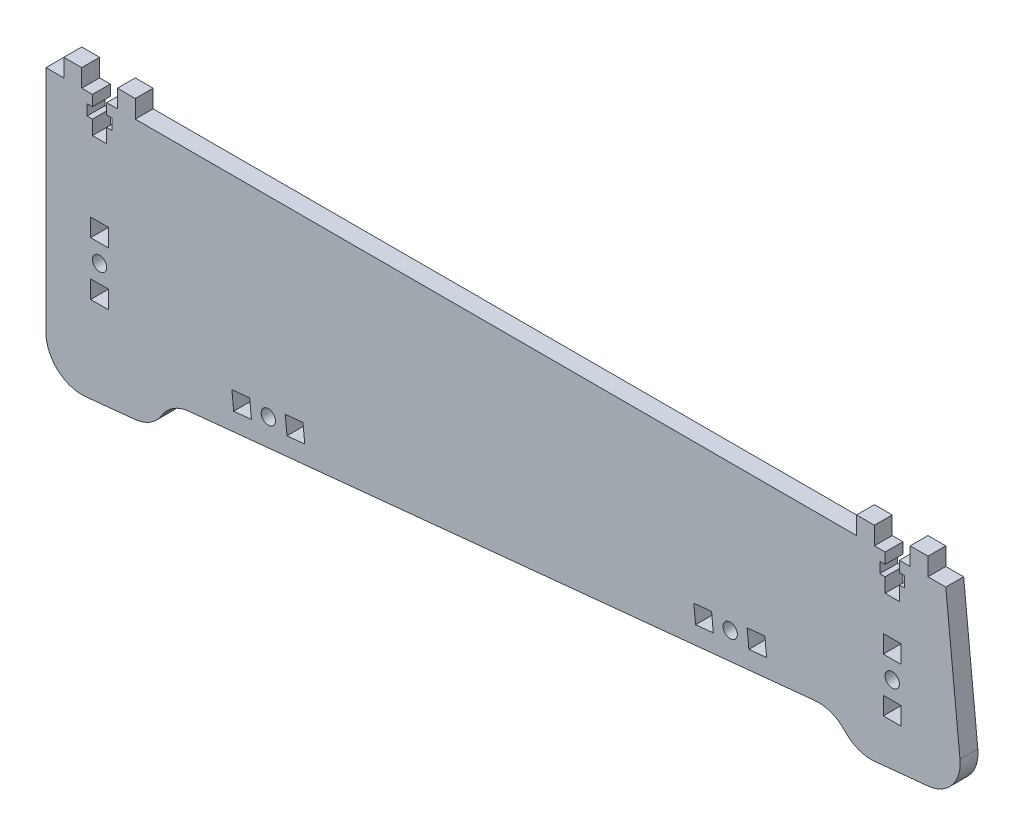
SolidWorks part; units mm, degrees
ref_plane "Plan de face" through (0, 0, 0) normal (0, 0, 1) x (1, 0, 0)
ref_plane "Plan de dessus" through (0, 0, 0) normal (0, 1, 0) x (1, 0, 0)
ref_plane "Plan de droite" through (0, 0, 0) normal (1, 0, 0) x (0, 0, -1)
sketch "Esquisse1" plane through (0, 0, 0) normal (0, 0, 1) x (1, 0, 0)
  line L0 (10, 0) -> (15, 0)
  line L1 (15, 0) -> (207, 0)
  line L4 (207, 0) -> (212, 0)
  line L5 (232, 0) -> (237, 0)
  line L6 (241.9603, -49.7533) -> (-15, -75.3718) construction
  line L7 (-15, -75.3718) -> (-15, 0)
  line L8 (-15, 0) -> (-10, 0)
  line L9 (237, 0) -> (241.9603, -49.7533)
  line L10 (-15, -75.3718) -> (14.852, -72.3956)
  line L11 (14.852, -72.3956) -> (20.0288, -63.8399)
  line L12 (20.0288, -63.8399) -> (205.3443, -45.3642)
  line L13 (205.3443, -45.3642) -> (212.1083, -52.7295)
  line L14 (212.1083, -52.7295) -> (241.9603, -49.7533)
  line L15 (113.4802, -62.5626) -> (112.6865, -54.602) construction
  point P4 (0, -32.9517)
  point P5 (0, 0)
  point P19 (0, 0)
  point P20 (44.148, -52.7295)
  point P21 (174.4007, -41.6472)
  point P22 (113.0833, -58.5823)
  line B0 (3.5, -3) -> (3.5, -6)
  line B1 (-2, -6) -> (-2, -10)
  line B2 (2, -10) -> (2, -6)
  line B3 (3.5, -6) -> (2, -6)
  line B4 (0, 0) -> (0, -11.2208) construction
  line B5 (2, 0) -> (5, 0)
  line B6 (5, 5) -> (10, 5)
  line B7 (10, 5) -> (10, 0)
  line B8 (5, 5) -> (5, 0)
  line B9 (-2, 0) -> (-5, 0)
  line B10 (-5, 0) -> (-5, 5)
  line B11 (-5, 5) -> (-10, 5)
  line B12 (-10, 5) -> (-10, 0)
  line B13 (2, 0) -> (-2, 0) construction
  line B14 (-2, 0) -> (-2, -3)
  line B15 (-2, -6) -> (-3.5, -6)
  line B16 (-3.5, -3) -> (-2, -3)
  line B17 (-2, -10) -> (2, -10)
  line B18 (2, -3) -> (3.5, -3)
  line B19 (-3.5, -6) -> (-3.5, -3)
  line B20 (2, -3) -> (2, 0)
  line B21 (0, -10) -> (0, 0) construction
  line B22 (225.5, -3) -> (225.5, -6)
  line B23 (220, -6) -> (220, -10)
  line B24 (224, -10) -> (224, -6)
  line B25 (225.5, -6) -> (224, -6)
  line B26 (222, 0) -> (222, -11.2208) construction
  line B27 (224, 0) -> (227, 0)
  line B28 (227, 5) -> (232, 5)
  line B29 (232, 5) -> (232, 0)
  line B30 (227, 5) -> (227, 0)
  line B31 (220, 0) -> (217, 0)
  line B32 (217, 0) -> (217, 5)
  line B33 (217, 5) -> (212, 5)
  line B34 (212, 5) -> (212, 0)
  line B35 (224, 0) -> (220, 0) construction
  line B36 (220, 0) -> (220, -3)
  line B37 (220, -6) -> (218.5, -6)
  line B38 (218.5, -3) -> (220, -3)
  line B39 (220, -10) -> (224, -10)
  line B40 (224, -3) -> (225.5, -3)
  line B41 (218.5, -6) -> (218.5, -3)
  line B42 (224, -3) -> (224, 0)
  line B43 (222, -10) -> (222, 0) construction
  line B44 (0, -35) -> (0, -45) construction
  line B45 (2.5, -35) -> (2.5, -30)
  line B46 (2.5, -35) -> (-2.5, -35)
  line B47 (-2.5, -35) -> (-2.5, -30)
  line B48 (2.5, -30) -> (-2.5, -30)
  line B49 (2.5, -45) -> (2.5, -50)
  line B50 (2.5, -45) -> (-2.5, -45)
  line B51 (-2.5, -45) -> (-2.5, -50)
  line B52 (2.5, -50) -> (-2.5, -50)
  line B53 (0, -40) -> (6.9724, -40) construction
  circle B54 centre (0, -40) radius 2
  line B55 (222, -25) -> (222, -35) construction
  line B56 (224.5, -25) -> (224.5, -20)
  line B57 (224.5, -25) -> (219.5, -25)
  line B58 (219.5, -25) -> (219.5, -20)
  line B59 (224.5, -20) -> (219.5, -20)
  line B60 (224.5, -35) -> (224.5, -40)
  line B61 (224.5, -35) -> (219.5, -35)
  line B62 (219.5, -35) -> (219.5, -40)
  line B63 (224.5, -40) -> (219.5, -40)
  line B64 (222, -30) -> (228.9724, -30) construction
  circle B65 centre (222, -30) radius 2
  line B66 (52.2384, -53.0914) -> (42.2878, -54.0835) construction
  line B67 (52.4865, -55.5791) -> (57.4618, -55.0831)
  line B68 (52.4865, -55.5791) -> (51.9904, -50.6038)
  line B69 (51.9904, -50.6038) -> (56.9658, -50.1077)
  line B70 (57.4618, -55.0831) -> (56.9658, -50.1077)
  line B71 (42.5358, -56.5712) -> (37.5605, -57.0672)
  line B72 (42.5358, -56.5712) -> (42.0398, -51.5958)
  line B73 (42.0398, -51.5958) -> (37.0644, -52.0919)
  line B74 (37.5605, -57.0672) -> (37.0644, -52.0919)
  line B75 (47.2631, -53.5875) -> (47.9548, -60.5255) construction
  circle B76 centre (47.2631, -53.5875) radius 2
  line B77 (181.5971, -40.1946) -> (171.6465, -41.1867) construction
  line B78 (181.8452, -42.6823) -> (186.8205, -42.1862)
  line B79 (181.8452, -42.6823) -> (181.3491, -37.7069)
  line B80 (181.3491, -37.7069) -> (186.3245, -37.2109)
  line B81 (186.8205, -42.1862) -> (186.3245, -37.2109)
  line B82 (171.8945, -43.6743) -> (166.9192, -44.1704)
  line B83 (171.8945, -43.6743) -> (171.3985, -38.699)
  line B84 (171.3985, -38.699) -> (166.4231, -39.195)
  line B85 (166.9192, -44.1704) -> (166.4231, -39.195)
  line B86 (176.6218, -40.6906) -> (177.3135, -47.6287) construction
  circle B87 centre (176.6218, -40.6906) radius 2
  dimension "D1" = 222
  dimension "D2" = 5
  dimension "D3" = 40
  dimension "D4" = 8
  dimension "D5" = 50
  dimension "D6" = 75
  dimension "D7" = 30
  dimension "D8" = 10
  dimension "D9" = 30
  dimension "D10" = 130
  dimension "D11" = 65
  dimension "D12" = 5
sketch_block_instance "Insert M4 plots ep 5mm-1"
sketch_block "Insert M4 plots ep 5mm" parameters "D1"=10, "D2"=5, "D3"=5, "D4"=7, "D5"=4, "D6"=3, "D7"=3, "D8"=10
sketch_block_instance "Insert M4 plots ep 5mm-2"
sketch_block_instance "Trou M4 plots 5mm-1"
sketch_block "Trou M4 plots 5mm" parameters "D2"=4, "D1"=5, "D3"=5, "D4"=10
sketch_block_instance "Trou M4 plots 5mm-3"
sketch_block_instance "Trou M4 plots 5mm-4"
sketch_block_instance "Trou M4 plots 5mm-5"
extrude "Boss.-Extru.1" add sketch "Esquisse1" along normal blind 5 contours B42 B40 B22 B25 B24 B39 B23 B37 B41 B38 B36 B31 B32 B33 B34 L4 L0 B7 B6 B8 B5 B20 B18 B0 B3 B2 B17 B1 B15 B19 B16 B14 B9 B10 B11 B12 L8 L7 L6 L9 L5 B29 B28 B30 B27 region at (102.5028, -28.7082, 0)
fillet "Congé1" radius 10 6 edges at (241.9603, -49.7533, 2.5) (205.3443, -45.3642, 2.5) (212.1083, -52.7295, 2.5) (-15, -75.3718, 2.5) (20.0288, -63.8399, 2.5) (14.852, -72.3956, 2.5)
